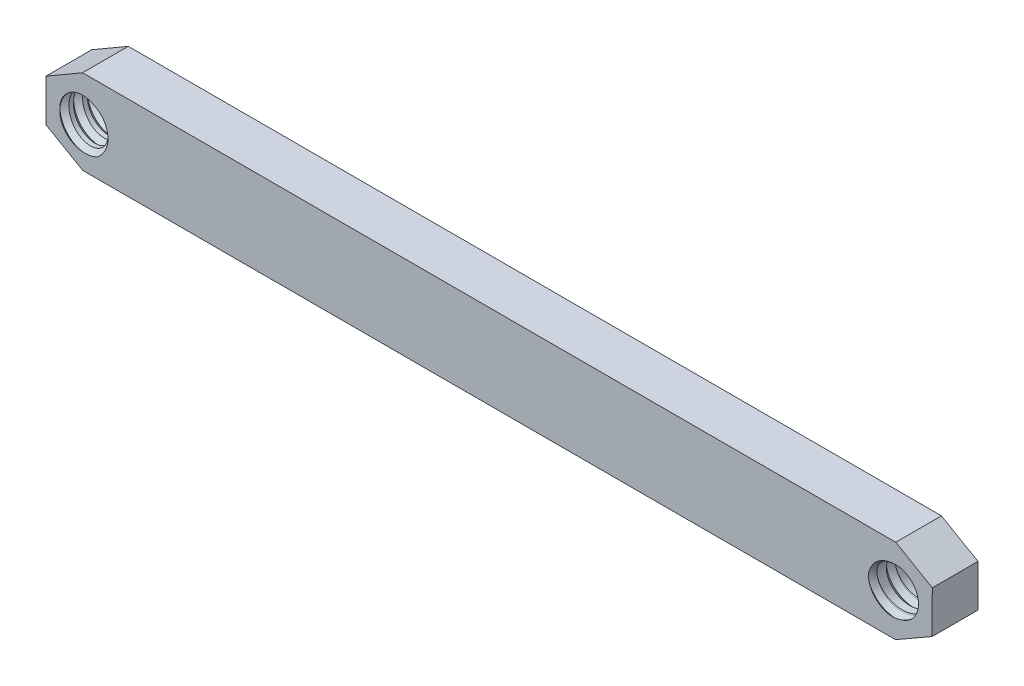
SolidWorks part; units mm, degrees
other "Markup1"
sketch "Sketch13"
ref_plane "Front Plane" through (0, 0, 0) normal (0, 0, 1) x (1, 0, 0)
ref_plane "Top Plane" through (0, 0, 0) normal (0, 1, 0) x (1, 0, 0)
ref_plane "Right Plane" through (0, 0, 0) normal (1, 0, 0) x (0, 0, -1)
sketch "Sketch1" plane through (0, 0, 0) normal (0, 0, 1) x (1, 0, 0)
  line L1 (-8.1676, -4.3156) -> (-0.3464, -9.2311)
  line L2 (-0.3464, -9.2311) -> (7.8212, -4.9156)
  line L3 (7.8212, -4.9156) -> (8.1676, 4.3156)
  line L4 (8.1676, 4.3156) -> (0.3464, 9.2311)
  line L5 (0.3464, 9.2311) -> (-7.8212, 4.9156)
  line L6 (-7.8212, 4.9156) -> (-8.1676, -4.3156)
  circle A0 centre (0, 0) radius 8 construction
sketch "Sketch2" plane through (0, 0, 0) normal (0, 0, 1) x (1, 0, 0)
  circle A0 centre (0, 0) radius 5
  dimension "D1" = 10
extrude "Boss-Extrude1" add sketch "Sketch1" along normal blind 10
extrude "Cut-Extrude1" cut sketch "Sketch2" against normal blind 10 and the other way blind 10 contours A0
sketch "Sketch3" plane through (0, 0, 0) normal (0, 0, 1) x (1, 0, 0)
  circle A0 centre (0, 0) radius 5
curve "Helix/Spiral1" pitch 4 height 10 radius 5 left hand yes centre (0, 0, 0) axis (0, 0, 1) start towards (1, 0, 0)
move or copy body "Body-Move/Copy1" bodies to move or copy 102 copy no rotation origin (-4.9965, 0, 0) rotation axis (0, 0, 1) rotation angle 2
sketch "Sketch21" plane through (0, 0, 0) normal (0, 1, 0) x (1, 0, 0)
  line L0 (4.997, 0) -> (5.997, 0) construction
  line L1 (8.0089, 0) -> (0.021, 0) construction
  line L2 (4.997, -1) -> (4.997, 1) construction
  line L3 (5.997, 0) -> (4.997, 1)
  line L4 (5.997, 0) -> (4.997, -1)
  line L5 (4.997, 1) -> (4.2898, 1.7071)
  line L6 (4.997, -1) -> (4.2898, -1.7071)
  line L7 (4.2898, -1.7071) -> (4.2898, 1.7071)
  point P8 (4.997, 0)
  dimension "D1" = 1
  dimension "D2" = 45
  dimension "D3" = 1
sweep "Cut-Sweep1" cut profiles "Sketch21" path "Helix/Spiral1" align with end faces yes
sketch "Sketch26" plane through (0, 0, 10) normal (0, 0, 1) x (1, 0, 0)
  line L0 (-8.015, -4.4236) -> (-0.0271, -9.0632) construction
  line L1 (-7.991, 4.814) -> (-8.015, -4.4236) construction
  line L2 (0.021, 9.4119) -> (-7.991, 4.814) construction
  line L3 (-8.015, -4.4236) -> (-0.0271, -9.0632)
  line L4 (-7.991, 4.814) -> (-8.015, -4.4236)
  line L5 (0.021, 9.4119) -> (-7.991, 4.814)
  line L6 (0.021, 9.4119) -> (-177.779, 9.4119)
  line L7 (-88.879, 9.4119) -> (-88.879, -24.4636) construction
  line L8 (-185.767, 4.7723) -> (-177.779, 9.4119)
  line L12 (-0.0271, -9.0632) -> (7.9849, -4.4652) construction
  line L13 (7.9849, -4.4652) -> (8.0089, 4.7723) construction
  line L14 (8.0089, 4.7723) -> (0.021, 9.4119) construction
  line L15 (-0.0271, -9.0632) -> (7.9849, -4.4652)
  line L16 (7.9849, -4.4652) -> (8.0089, 4.7723)
  line L17 (8.0089, 4.7723) -> (0.021, 9.4119)
  line L21 (-185.7429, -4.4652) -> (-185.767, 4.7723)
  line L22 (-177.7309, -9.0632) -> (-185.7429, -4.4652)
  line L23 (-177.7309, -9.0632) -> (-0.0271, -9.0632)
  line M6 (-7.991, 4.814) -> (-8.015, -4.4236)
  line M7 (-8.015, -4.4236) -> (-0.0271, -9.0632)
  line M11 (0.021, 9.4119) -> (-7.991, 4.814)
  dimension "D1" = 177.8
extrude "Boss-Extrude2" add sketch "Sketch26" against normal blind 10 contours L6 L7 L23 M7 M6 M11 | L7 L6 L8 L21 L22 L23 region at (-47.4008, 0.1746, 10) region at (-136.3521, 0.1746, 10)
sketch "Sketch27" plane through (0, 0, 0) normal (0, 0, -1) x (-1, 0, 0)
  line L0 (177.7309, -9.0632) -> (185.7429, -4.4652) construction
  line L1 (185.7429, -4.4652) -> (185.767, 4.7723) construction
  line L2 (185.767, 4.7723) -> (177.779, 9.4119) construction
  line L3 (177.7309, -9.0632) -> (185.7429, -4.4652)
  line L4 (185.7429, -4.4652) -> (185.767, 4.7723)
  line L5 (185.767, 4.7723) -> (177.779, 9.4119)
  line L6 (177.779, 9.4119) -> (177.7309, -9.0632) construction
  circle A0 centre (177.755, 0.1744) radius 5
  dimension "D1" = 10
extrude "Cut-Extrude6" cut sketch "Sketch27" against normal blind 10 contours A0 L6 | L6 A0 region at (-175.6329, 0.1799, 0) region at (-179.877, 0.1689, 0)
sketch "Sketch29" plane through (0, 0, 0) normal (0, 0, -1) x (-1, 0, 0)
  circle A0 centre (177.755, 0.1744) radius 5 construction
  circle A1 centre (177.755, 0.1744) radius 5
curve "Helix/Spiral2" pitch 3 height 10 radius 5 centre (-177.755, 0.1744, 0) axis (0, 0, 1) start towards (-1, 0, 0)
sketch "Sketch31" plane through (0, 0, 0) normal (0, -1, 0) x (1, 0, 0)
  line L0 (-182.755, 1) -> (-182.755, -1) construction
  line L2 (-182.755, -1) -> (-183.755, 0)
  line L3 (-185.767, 0) -> (-177.779, 0) construction
  line L4 (-182.755, 0) -> (-183.755, 0) construction
  line L5 (-183.755, 0) -> (-182.755, 1)
  line L6 (-182.755, 1) -> (-182.2457, 1.5093)
  line L7 (-182.2457, 1.5093) -> (-182.2457, -1.5093)
  line L8 (-182.755, -1) -> (-182.2457, -1.5093)
  point P4 (-182.755, 0)
  dimension "D1" = 1
  dimension "D2" = 45
sweep "Cut-Sweep4" cut profiles "Sketch31" path "Helix/Spiral2" align with end faces yes
